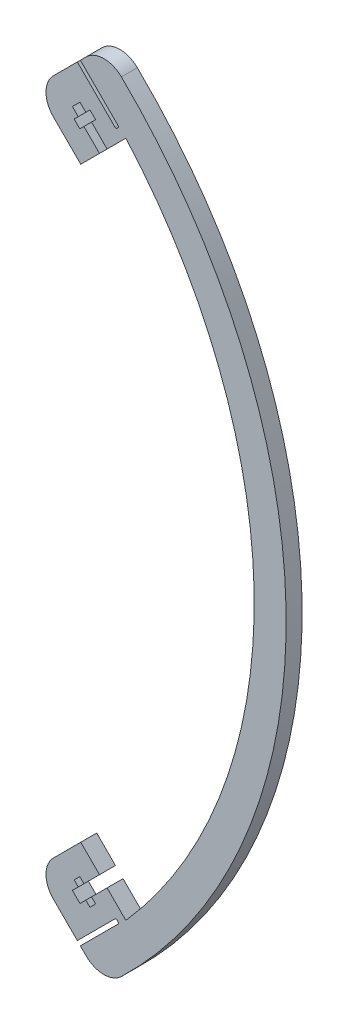
SolidWorks part; units mm, degrees
ref_plane "Front Plane" through (0, 0, 0) normal (0, 0, 1) x (1, 0, 0)
ref_plane "Top Plane" through (0, 0, 0) normal (0, 1, 0) x (1, 0, 0)
ref_plane "Right Plane" through (0, 0, 0) normal (1, 0, 0) x (0, 0, -1)
sketch "Sketch1" plane through (0, 0, 0) normal (0, 0, 1) x (1, 0, 0)
  line L0 (143.3604, 116.9193) -> (134.3442, 107.9031)
  line L1 (143.3604, -160.8213) -> (134.3442, -151.805)
  line L2 (143.3604, -160.8213) -> (128.1057, -145.5666) construction
  line L3 (128.1057, 101.6647) -> (143.3604, 116.9193) construction
  arc A0 (143.3604, 116.9193) -> (143.3604, -160.8213) centre (-21.951, -21.951) cw
  arc A1 (134.3442, 107.9031) -> (134.3442, -151.805) centre (-21.951, -21.951) cw
  arc A2 (143.3604, 116.9193) -> (-105.4853, 177.134) centre (-21.951, -21.951) ccw construction
  dimension "D1" = 12.7
extrude "Arc Extrusion" add sketch "Sketch1" along normal blind 6.35
ref_plane "Clothes Line Center Plane" through (0, -21.951, 0) normal (0, 1, 0) x (1, 0, 0)
sketch "Sketch4" plane through (0, 0, 6.35) normal (0, 0, 1) x (1, 0, 0)
  line L0 (134.3442, -151.805) -> (143.3604, -160.8213)
  line L1 (139.4438, -165.8849) -> (130.4636, -156.9046) construction
  line L2 (105.6551, -132.0962) -> (123.6156, -150.0567) construction
  line L3 (139.194, -165.6351) -> (112.2532, -138.6943)
  line L4 (112.2532, -138.6943) -> (94.2927, -156.6548)
  line L5 (94.2927, -156.6548) -> (121.204, -183.5661)
  arc A0 (143.3604, -160.8213) -> (139.194, -165.6351) centre (-21.951, -21.951) cw
  arc A1 (134.3442, -151.805) -> (130.1981, -156.6392) centre (-21.951, -21.951) cw
  arc A2 (139.194, -165.6351) -> (121.204, -183.5661) centre (-21.951, -21.951) cw
  arc A3 (134.3442, -151.805) -> (134.3442, 107.9031) centre (-21.951, -21.951) ccw construction
  arc A4 (143.3604, -160.8213) -> (143.3604, 116.9193) centre (-21.951, -21.951) ccw construction
  arc A5 (-217.6733, 69.184) -> (143.3604, -160.8213) centre (-21.951, -21.951) ccw construction
  line M8 (134.3442, -151.805) -> (143.3604, -160.8213)
  dimension "D1" = 25.4
  dimension "D2" = 38.1
extrude "Mount to V Funnel" add sketch "Sketch4" against normal up to surface (6.35 mm away) contours A1 L3 A0 M8 | A2 L3 L4 L5 region at (136.7864, -158.7357, 6.35) region at (116.8258, -161.2242, 6.35) up to face at (163.2257, -21.951, 0)
sketch "Sketch5" plane through (0, 0, 6.35) normal (0, 0, 1) x (1, 0, 0)
  line L0 (121.2256, -147.6667) -> (103.2651, -165.6272) construction
  line L1 (130.1981, -156.6392) -> (112.2532, -138.6943) construction
  line L2 (94.2927, -156.6548) -> (121.204, -183.5661) construction
  line L3 (130.1981, -156.6392) -> (112.2376, -174.5997)
  line L4 (112.2532, -138.6943) -> (94.2927, -156.6548) construction
  line B0 (122.7343, -149.1754) -> (119.717, -146.158)
  line B1 (111.2755, -154.5995) -> (109.6411, -152.9651)
  line B2 (109.6411, -152.9651) -> (111.8862, -150.72)
  line B3 (111.8862, -150.72) -> (113.5206, -152.3544)
  line B4 (113.5206, -152.3544) -> (119.717, -146.158)
  line B5 (111.2755, -154.5995) -> (108.9406, -156.9344)
  line B6 (108.9406, -156.9344) -> (111.958, -159.9517)
  line B7 (114.2929, -157.6169) -> (111.958, -159.9517)
  line B8 (116.5379, -155.3718) -> (122.7343, -149.1754)
  line B9 (118.1723, -157.0062) -> (116.5379, -155.3718)
  line B10 (115.9273, -159.2513) -> (118.1723, -157.0062)
  line B11 (114.2929, -157.6169) -> (115.9273, -159.2513)
  line M9 (130.1981, -156.6392) -> (112.2532, -138.6943)
sketch_block_instance "TSlot-1"
sketch_block "TSlot" parameters "D1"=3.302, "D2"=3.175
extrude "T Slot Hole" cut sketch "Sketch5" against normal through all contours L0 B6 B7 B11 B10 B9 B8 M9 | L0 B0 B4 B3 B2 B1 B5 B6 region at (116.5257, -154.4541, 6.35) region at (114.4382, -152.3667, 6.35)
mirror "Mount and T Slot Mirror" about plane through (0, -21.951, 0) normal (0, 1, 0) of "Mount to V Funnel", "T Slot Hole"
fillet "Mount Fillets" radius 10 4 edges at (94.2927, -156.6548, 3.175) (121.204, -183.5661, 3.175) (94.2927, 112.7529, 3.175) (121.204, 139.6642, 3.175)
sketch "Sketch6" plane through (0, 0, 6.35) normal (0, 0, 1) x (1, 0, 0)
  line L0 (110.8983, 129.3585) -> (126.2567, 114.0002)
  line L1 (101.3638, 119.8239) -> (114.3962, 132.8564) construction
  line L2 (126.2567, 114.0002) -> (127.4588, 115.2023)
  line L3 (127.4588, 115.2023) -> (112.1004, 130.5606)
  line L4 (115.9273, 115.3493) -> (118.1723, 113.1043) construction
  dimension "D1" = 1.7
  dimension "D2" = 21.72
  dimension "D3" = 6.35
extrude "Cut-Extrude1" cut sketch "Sketch6" against normal through all and the other way through all
mirror "Mirror1" about plane through (0, -21.951, 0) normal (0, 1, 0) of "Cut-Extrude1"
fillet "Fillet1" radius 0.5 4 edges at (127.4588, -159.1042, 3.175) (126.2567, -157.9021, 3.175) (126.2567, 114.0002, 3.175) (127.4588, 115.2023, 3.175)
